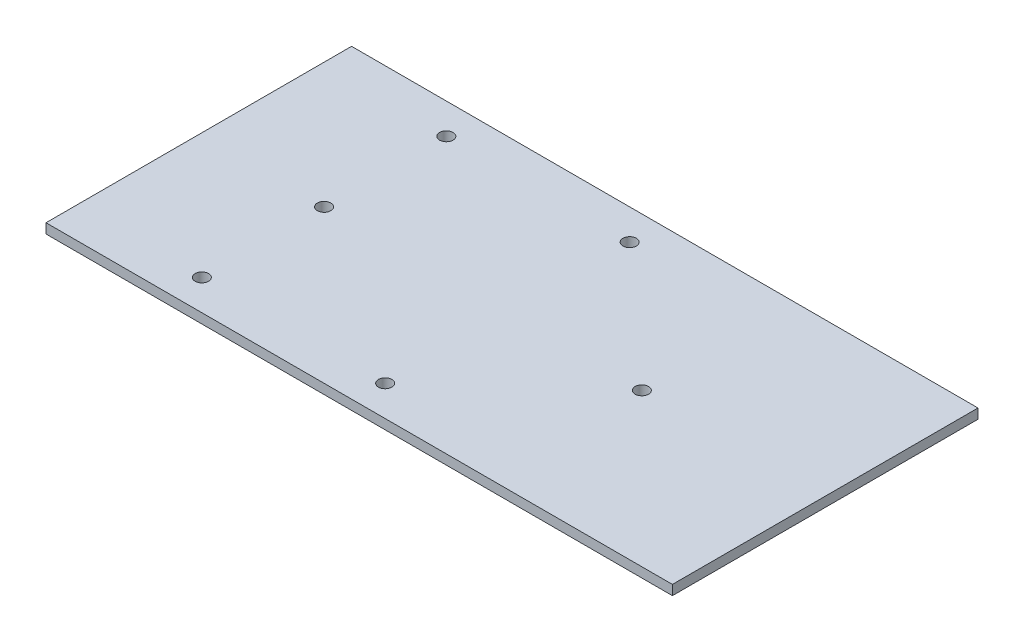
SolidWorks part; units mm, degrees
ref_plane "Front Plane" through (0, 0, 0) normal (0, 0, 1) x (1, 0, 0)
ref_plane "Top Plane" through (0, 0, 0) normal (0, 1, 0) x (1, 0, 0)
ref_plane "Right Plane" through (0, 0, 0) normal (1, 0, 0) x (0, 0, -1)
sketch "Sketch1" plane through (0, 0, 0) normal (0, 1, 0) x (1, 0, 0)
  line L1 (0, 0) -> (102.5, 0)
  line L2 (0, 0) -> (0, 50)
  line L3 (0, 50) -> (102.5, 50)
  line L4 (102.5, 0) -> (102.5, 50)
  dimension "D1" = 50
  dimension "D2" = 102.5
extrude "Boss-Extrude1" add sketch "Sketch1" along normal blind 1.6 contours L1 L4 L3 L2
sketch "Sketch2" plane through (0, 1.6, 0) normal (0, 1, 0) x (1, 0, 0)
  line L0 (0, 0) -> (0, 50) construction
  line L1 (0, 0) -> (102.5, 0) construction
  circle A0 centre (20.5, 5) radius 1.1
  circle A1 centre (20.5, 25) radius 1.1
  circle A2 centre (20.5, 45) radius 1.1
  circle A3 centre (50.5, 45) radius 1.1
  circle A4 centre (50.5, 5) radius 1.1
  circle A5 centre (72.5, 25) radius 1.1
  dimension "D1" = 2.2
  dimension "D2" = 20.5
  dimension "D3" = 5
  dimension "D4" = 25
  dimension "D5" = 45
  dimension "D6" = 50.5
  dimension "D7" = 72.5
extrude "Cut-Extrude1" cut sketch "Sketch2" against normal through all
